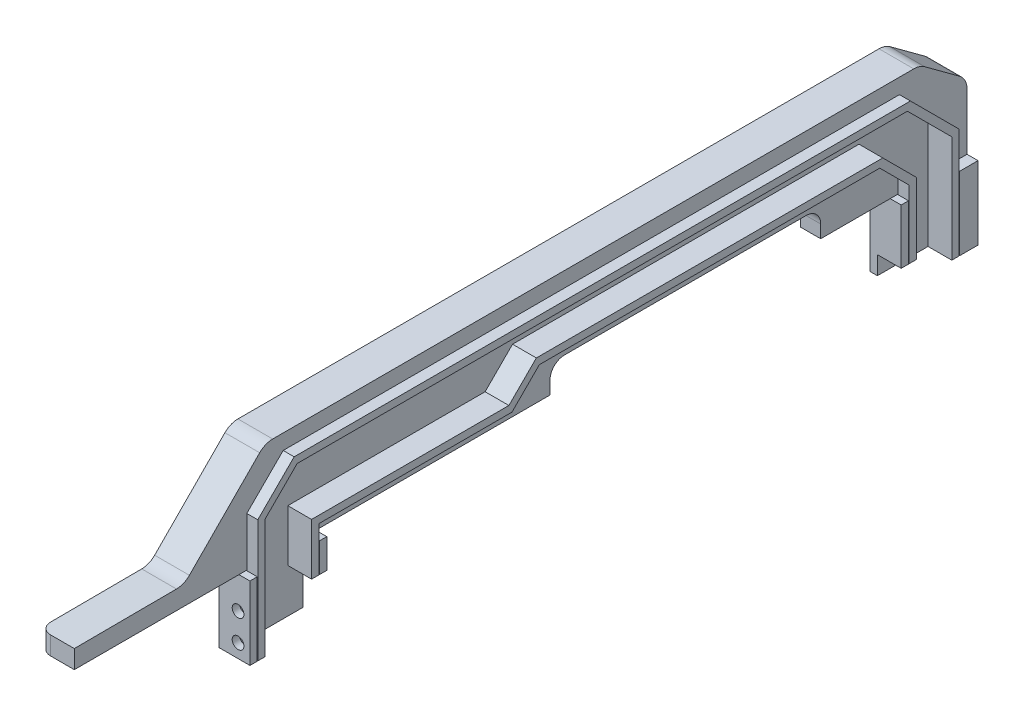
SolidWorks part; units mm, degrees
ref_plane "Front Plane" through (0, 0, 0) normal (0, 0, 1) x (1, 0, 0)
ref_plane "Top Plane" through (0, 0, 0) normal (0, 1, 0) x (1, 0, 0)
ref_plane "Right Plane" through (0, 0, 0) normal (1, 0, 0) x (0, 0, -1)
sketch "Sketch1" plane through (0, 0, 0) normal (1, 0, 0) x (0, 0, -1)
  line L0 (0, 0) -> (-130, 0)
  line L1 (0, 0) -> (74, 0) construction
  line L2 (0, 0) -> (0, 7.5)
  line L3 (0, 7.5) -> (74, 7.5)
  line L4 (74, 7.5) -> (74, 0)
  line L5 (74, 0) -> (114, 0)
  line L6 (-130, 0) -> (-130, 5)
  line L7 (-130, 5) -> (-100.0004, 5.1483)
  line L8 (-100.0004, 5.1483) -> (-77.8685, 27.5)
  line L9 (114, 0) -> (114, 18)
  line L10 (114, 18) -> (101.0882, 27.5)
  line L11 (101.0882, 27.5) -> (-77.8685, 27.5)
  dimension "D1" = 130
  dimension "D2" = 74
  dimension "D3" = 7.5
  dimension "D4" = 40
  dimension "D5" = 30
  dimension "D6" = 5
  dimension "D7" = 135
  dimension "D8" = 20
  dimension "D9" = 18
extrude "Boss-Extrude1" add sketch "Sketch1" along normal blind 25
sketch "Sketch4" plane through (25, 0, 0) normal (1, 0, 0) x (0, 0, -1)
  line L11 (-130, 0) -> (0, 0) construction
  line L12 (-130, 0) -> (0, 0) construction
  line L13 (-100.8762, 0) -> (0, 0)
  line L14 (0, 0) -> (111, 0)
  line L15 (74, 0) -> (114, 0) construction
  line L16 (111, 0) -> (111, 3)
  line L22 (-3, 3) -> (-3, 10.5)
  line L23 (-3, 10.5) -> (77, 10.5)
  line L24 (77, 10.5) -> (77, 3)
  line L25 (77, 3) -> (111, 3)
  line L26 (111, 3) -> (111, 16.4828)
  line L27 (111, 16.4828) -> (100.1035, 24.5)
  line L28 (100.1035, 24.5) -> (-76.6172, 24.5)
  line L29 (-76.6172, 24.5) -> (-97.9057, 3)
  line L30 (-97.9057, 3) -> (-3, 3)
  line L35 (111, 3) -> (111, 16.4828)
  line L36 (111, 16.4828) -> (100.1035, 24.5)
  line L37 (100.1035, 24.5) -> (-76.6172, 24.5)
  line L38 (-76.6172, 24.5) -> (-100.8762, 0)
  dimension "D1" = 3
extrude "Cut-Extrude1" cut sketch "Sketch4" against normal blind 4
ref_plane "Plane1" through (12.5, 0, 0) normal (1, 0, 0) x (0, 0, -1)
mirror "Mirror2" about plane through (12.5, 0, 0) normal (1, 0, 0) of "Cut-Extrude1"
fillet "Fillet1" radius 4 2 edges at (12.5, 7.5, -74) (12.5, 7.5, 0)
fillet "Fillet2" radius 10 8 edges at (23, 16.4828, -111) (23, 24.5, -100.1035) (2, 16.4828, -111) (2, 24.5, -100.1035) (2, 24.5, 76.6172) (23, 24.5, 76.6172) (2, 0, 100.8762) (23, 0, 100.8762)
fillet "Fillet3" radius 5 4 edges at (12.5, 18, -114) (12.5, 27.5, -101.0882) (12.5, 27.5, 77.8685) (12.5, 5.1483, 100.0004)
fillet "Fillet4" radius 3 2 edges at (0, 2.5, 130) (25, 2.5, 130)
sketch "Sketch5" plane through (12.5, 0, 0) normal (1, 0, 0) x (0, 0, -1)
  line L0 (-117.866, 5.06) -> (-103.7939, 19.2718)
  line L1 (-102.0714, 5.138) -> (-127, 5.0148) construction
  line L2 (-79.3359, 26.018) -> (-98.5432, 6.62) construction
  line L3 (-103.7939, 19.2718) -> (-72.6053, 19.2718)
  line L4 (-117.866, 5.06) -> (-95.866, 5.06)
  line L5 (-79.552, 21.536) -> (-97.9414, 2.964) construction
  line L6 (-72.6053, 19.2718) -> (-95.866, 5.06)
  dimension "D1" = 22
  dimension "D2" = 20
extrude "Boss-Extrude2" add sketch "Sketch5" along normal blind 3 and the other way blind 3
fillet "Fillet5" radius 3 1 edges at (12.5, 19.2718, 103.7939)
sketch "Sketch6" plane through (0, 0, 0) normal (0, -1, 0) x (1, 0, 0)
  line L1 (0, -111) -> (0, -114) construction
  line L2 (0, -111) -> (4, -111)
  line L3 (0, -111) -> (0, -114)
  line L4 (0, -114) -> (25, -114)
  line L5 (25, -111) -> (25, -114)
  line L6 (0, -111) -> (25, -114) construction
  line L7 (0, -114) -> (25, -111) construction
  line L8 (4, -111) -> (0, -111) construction
  line L9 (25, -114) -> (0, -114) construction
  line L10 (4, -74) -> (4, -111) construction
  line L11 (4, -111) -> (21, -111) construction
  line L12 (4, -111) -> (4, -93)
  line L13 (4, -93) -> (21, -93)
  line L14 (21, -111) -> (21, -93)
  line L15 (4, -111) -> (21, -93) construction
  line L16 (4, -93) -> (21, -111) construction
  line L17 (21, -74) -> (21, -111) construction
  line L18 (4, -111) -> (21, -111) construction
  line L19 (21, -111) -> (25, -111)
  line L21 (19, -95) -> (6, -95)
  line L22 (19, -95) -> (19, -109)
  line L23 (19, -109) -> (6, -109)
  line L24 (6, -95) -> (6, -109)
  line L25 (19, -95) -> (6, -109) construction
  line L26 (19, -109) -> (6, -95) construction
  point P6 (12.5, -112.5)
  point P16 (12.5, -102)
  point P21 (12.5, -102)
  dimension "D1" = 18
  dimension "D2" = 2
  dimension "D3" = 2
extrude "Boss-Extrude3" add sketch "Sketch6" along normal blind 20
sketch "Sketch7" plane through (0, -20, 0) normal (0, -1, 0) x (1, 0, 0)
  line L0 (19, -109) -> (19, -95) construction
  line L1 (19, -95) -> (6, -95)
  line L2 (19, -95) -> (19, -93)
  line L3 (19, -93) -> (6, -93)
  line L4 (6, -95) -> (6, -93)
  line L5 (19, -95) -> (6, -93) construction
  line L6 (19, -93) -> (6, -95) construction
  line L7 (19, -95) -> (6, -95) construction
  line L8 (21, -93) -> (4, -93) construction
  line L9 (6, -95) -> (6, -109) construction
  point P4 (12.5, -94)
sketch "Sketch8" plane through (0, 0, 0) normal (0, -1, 0) x (1, 0, 0)
  line L5 (21, 85) -> (21, 130) construction
  line L6 (21, 105.0473) -> (21, 0) construction
  line L8 (22, 130) -> (3, 130) construction
  line L9 (4, 105.0473) -> (4, 0) construction
  line L10 (21, 85) -> (4, 85)
  line L11 (21, 85) -> (21, 64)
  line L12 (21, 64) -> (19, 64)
  line L13 (4, 85) -> (4, 64)
  line L14 (21, 85) -> (4, 64) construction
  line L15 (21, 64) -> (4, 85) construction
  line L16 (19, 64) -> (6, 64) construction
  line L17 (6, 64) -> (19, 64) construction
  line L18 (6, 64) -> (6, 83)
  line L19 (6, 83) -> (19, 83)
  line L20 (19, 64) -> (19, 83)
  line L21 (6, 64) -> (19, 83) construction
  line L22 (6, 83) -> (19, 64) construction
  line L23 (6, 64) -> (4, 64)
  point P9 (12.5, 74.5)
  point P16 (12.5, 73.5)
  dimension "D1" = 45
  dimension "D2" = 21
  dimension "D3" = 2
  dimension "D4" = 2
  dimension "D5" = 2
extrude "Boss-Extrude4" add sketch "Sketch8" along normal blind 20
sketch "Sketch9" plane through (0, 0, 0) normal (0, -1, 0) x (1, 0, 0)
  line L0 (6, 64) -> (6, 83) construction
  line L1 (6, 64) -> (19, 64)
  line L2 (6, 64) -> (6, 66)
  line L3 (6, 66) -> (19, 66)
  line L4 (19, 64) -> (19, 66)
  line L5 (6, 64) -> (19, 66) construction
  line L6 (6, 66) -> (19, 64) construction
  line L7 (19, 83) -> (19, 64) construction
  point P4 (12.5, 65)
  dimension "D1" = 2
extrude "Boss-Extrude5" add sketch "Sketch9" along normal blind 8
extrude "Cut-Extrude2" cut sketch "Sketch7" against normal blind 5 contours L3 L4 L1 L2
sketch "Sketch11" plane through (0, 0, -114) normal (0, 0, -1) x (-1, 0, 0)
  line L0 (0, -20) -> (0, -12.5) construction
  line L1 (0, -20) -> (-25, -20) construction
  line L2 (0, -20) -> (0, 15.4713) construction
  line L3 (0, -16.25) -> (-25, -16.25) construction
  line L4 (-25, -20) -> (-25, 15.4713) construction
  line L5 (0, -16.25) -> (-9.25, -16.25) construction
  line L6 (-12.5, -20) -> (-12.5, -5) construction
  line L7 (0, -20) -> (0, -16.25)
  line L8 (-25, -20) -> (-25, -12.5) construction
  line L9 (-25, -12.5) -> (0, -12.5) construction
  circle A0 centre (-9.25, -16.25) radius 1.6
  circle A1 centre (-15.75, -16.25) radius 1.6
  circle A2 centre (-15.75, -8.75) radius 1.6
  circle A3 centre (-9.25, -8.75) radius 1.6
  circle A4 centre (-15.75, -16.25) radius 3 construction
  dimension "D2" = 3.2
  dimension "D5" = 6
  dimension "D1" = 9.25
  dimension "D3" = 3.75
  dimension "D4" = 7.5
extrude "Cut-Extrude3" cut sketch "Sketch11" against normal up to surface (19 mm away) contours A1 | A2 | A3 | A0 region at (9.25, -16.25, -114) region at (15.75, -16.25, -114) region at (15.75, -8.75, -114) region at (9.25, -8.75, -114) up to face at (12.5, -7.5, -95)
sketch "Sketch12" plane through (0, 0, 85) normal (0, 0, 1) x (1, 0, 0)
  line L0 (15.75, -8.75) -> (21, -8.75) construction
  line L1 (15.75, -8.75) -> (15.75, -5) construction
  line L3 (12.5, -20) -> (12.5, -5) construction
  line L6 (0, -12.5) -> (25, -12.5) construction
  line L7 (4, -20) -> (21, -20) construction
  line L8 (4, -20) -> (4, 0) construction
  line L9 (21, -20) -> (21, 0) construction
  circle A0 centre (15.75, -16.25) radius 1.6
  circle A1 centre (9.25, -16.25) radius 1.6
  circle A2 centre (9.25, -8.75) radius 1.6
  circle A3 centre (15.75, -8.75) radius 1.6
  circle A4 centre (9.25, -16.25) radius 3 construction
  dimension "D1" = 3.2
  dimension "D2" = 5.25
  dimension "D3" = 3.75
extrude "Cut-Extrude4" cut sketch "Sketch12" against normal up to surface (2 mm away) up to face at (12.5, -10, 83)
sketch "MAKE THIS A SQUARE OR SMTH" plane through (4, 0, 0) normal (-1, 0, 0) x (0, 0, 1)
  line L0 (-37, 7.5) -> (-37, 24.5) construction
  line L1 (-70, 7.5) -> (-4, 7.5) construction
  line L2 (-96.8211, 24.5) -> (72.4461, 24.5) construction
  line L3 (-37, 16) -> (-111, 16) construction
  line L4 (-37, 16) -> (84, 16) construction
  line L6 (-111, 16) -> (-13.5, 16) construction
  line L7 (-13.5, 16) -> (-13.5, 7.5) construction
  line L8 (-111, 16) -> (-91, 16) construction
  circle A1 centre (-91, 16) radius 6.5
  circle A2 centre (-39.3333, 16) radius 6.5
  circle A3 centre (64, 16) radius 6.5
  circle A4 centre (12.3333, 16) radius 6.5
  dimension "D5" = 13
  dimension "D1" = 74
  dimension "D2" = 121
  dimension "D3" = 97.5
  dimension "D4" = 20
  dimension "D6" = 51.6667
sketch "Sketch14" plane through (12.5, 0, 0) normal (1, 0, 0) x (0, 0, -1)
  line L0 (-83, 0) -> (-83, 13.4752)
  line L1 (-66, 0) -> (-66, 4)
  line L2 (-66, 4) -> (-13.3251, 4)
  line L3 (-13.3251, 4) -> (-5.8251, 11.5)
  line L4 (-5.8251, 11.5) -> (87.0794, 11.5)
  line L5 (95, 0) -> (95, 3.5794)
  line L6 (95, 3.5794) -> (87.0794, 11.5)
  line L7 (109, 0) -> (109, 10.0924)
  line L8 (109, -20) -> (109, 0) construction
  line L9 (95, 0) -> (109, 0) construction
  line L10 (109, 10.0924) -> (95.5924, 23.5)
  line L15 (-72.9752, 23.5) -> (-83, 13.4752)
  line L16 (-83, 0) -> (-66, 0)
  line L17 (95, 0) -> (109, 0)
  line L18 (95.5924, 23.5) -> (-72.9752, 23.5)
  line L19 (-64, 0) -> (0, 0) construction
  line L20 (99.447, 27.5) -> (-75.783, 27.5) construction
  line L21 (70, 7.5) -> (4, 7.5) construction
  dimension "D1" = 135
  dimension "D2" = 135
  dimension "D3" = 135
  dimension "D4" = 135
  dimension "D5" = 4
  dimension "D6" = 4
  dimension "D7" = 4
extrude "Cut-Extrude5" cut sketch "Sketch14" against normal blind 6.5 and the other way blind 6.5
sketch "Sketch17" plane through (0, 0, 130) normal (0, 0, 1) x (1, 0, 0)
  line L0 (12.5, -20) -> (25, -20)
  line L1 (21, -20) -> (4, -20) construction
  line L2 (25, -20) -> (25, 27.5)
  line L3 (25, 27.5) -> (9.5, 27.5)
  line L4 (0, 27.5) -> (25, 27.5) construction
  line L5 (9.5, 5.138) -> (9.5, 27.5)
  line L6 (12.5, -20) -> (12.5, 0)
  line L7 (22, 0) -> (3, 0) construction
  line L8 (12.5, 0) -> (9.5, 0)
  line L9 (21, 0) -> (4, 0) construction
  line L10 (9.5, 0) -> (9.5, 5.138)
extrude "Cut-Extrude7" cut sketch "Sketch17" against normal through all
sketch "Sketch18" plane through (6, 0, 0) normal (1, 0, 0) x (0, 0, -1)
  line L0 (-83, -20) -> (-82.85, -20)
  line L1 (-64, -20) -> (-83, -20) construction
  line L2 (-82.85, -20) -> (-80.85, -20)
  line L3 (-66, -8) -> (-66.15, -8)
  line L4 (-66.15, -8) -> (-68.15, -8)
  line L5 (-66.15, -8) -> (-66.15, 4.15)
  line L6 (-66.15, 4.15) -> (-13.3872, 4.15)
  line L7 (-13.3872, 4.15) -> (-5.8872, 11.65)
  line L8 (-5.8872, 11.65) -> (87.1415, 11.65)
  line L9 (87.1415, 11.65) -> (95.15, 3.6415)
  line L10 (95.15, 3.6415) -> (95.15, -15)
  line L11 (95, -15) -> (95, 3.5794) construction
  line L12 (95, -15) -> (95.15, -15)
  line L13 (95, 3.5794) -> (87.0794, 11.5) construction
  line L14 (-47.2142, 4) -> (-47.2142, 4.15) construction
  line L15 (-13.3251, 4) -> (-66, 4) construction
  line L16 (-10.7524, 6.7848) -> (-10.6464, 6.6787) construction
  line L17 (-68.15, -10) -> (-68.15, 6.15) construction
  line L18 (-5.8251, 11.5) -> (-13.3251, 4) construction
  line L19 (91.2889, 7.2905) -> (91.3949, 7.3966) construction
  line L20 (61.1672, 11.5) -> (61.1672, 11.65) construction
  line L21 (-5.8251, 11.5) -> (87.0794, 11.5) construction
  line L22 (95.15, -15) -> (97.15, -15)
  line L23 (-68.15, -8) -> (-68.15, 6.15)
  line L24 (-68.15, 6.15) -> (-14.2157, 6.15)
  line L25 (-14.2157, 6.15) -> (-6.7157, 13.65)
  line L26 (-6.7157, 13.65) -> (87.97, 13.65)
  line L27 (87.97, 13.65) -> (97.15, 4.47)
  line L28 (97.15, 4.47) -> (97.15, -15)
  line L29 (-82.85, -20) -> (-82.85, 13.413)
  line L30 (-49.2142, 4) -> (-49.2142, 4.15) construction
  line L31 (-9.3382, 8.199) -> (-9.2321, 8.093) construction
  line L32 (89.8746, 8.7048) -> (89.9807, 8.8108) construction
  line L33 (59.1672, 11.5) -> (59.1672, 11.65) construction
  line L34 (-66, -10) -> (-68.15, -10) construction
  line L35 (97.15, 4.47) -> (97.15, -17) construction
  line L36 (95, -17) -> (97.15, -17) construction
  line L37 (-82.85, 13.413) -> (-72.913, 23.35)
  line L38 (-72.9752, 23.5) -> (-83, 13.4752) construction
  line L39 (-72.913, 23.35) -> (95.5303, 23.35)
  line L40 (-78.8315, 17.4315) -> (-78.9376, 17.5376) construction
  line L41 (-83, -20) -> (-83, 13.4752)
  line L42 (-68.3764, 23.35) -> (-68.3764, 23.5) construction
  line L43 (-72.9752, 23.5) -> (95.5924, 23.5) construction
  line L44 (95.5303, 23.35) -> (108.85, 10.0303)
  line L45 (108.85, 10.0303) -> (108.85, -20)
  line L46 (93, -20) -> (109, -20) construction
  line L47 (109, 10.0924) -> (95.5924, 23.5) construction
  line L48 (101.5774, 17.3029) -> (101.6835, 17.4089) construction
  line L49 (108.85, -12.75) -> (109, -12.75) construction
  line L50 (109, 0) -> (109, -20) construction
  line L51 (-80.85, -20) -> (-80.85, 12.5846)
  line L52 (-80.85, 12.5846) -> (-72.0846, 21.35)
  line L53 (-72.0846, 21.35) -> (94.7019, 21.35)
  line L54 (94.7019, 21.35) -> (106.85, 9.2019)
  line L55 (106.85, 9.2019) -> (106.85, -20)
  line L56 (-82.85, -20) -> (-80.85, -20)
  line L57 (106.85, -20) -> (108.85, -20)
  line L58 (-83, 13.4752) -> (-72.9752, 23.5) construction
  line L59 (-83, 13.4752) -> (-72.9752, 23.5)
  line L60 (-72.9752, 23.5) -> (95.5924, 23.5)
  line L61 (95.5924, 23.5) -> (109, 10.0924)
  line L62 (109, 10.0924) -> (109, -20)
  line L63 (109, -20) -> (108.85, -20)
  line L64 (-66, -8) -> (-66, 4)
  line L65 (-66, 4) -> (-13.3251, 4)
  line L66 (-13.3251, 4) -> (-5.8251, 11.5)
  line L67 (-5.8251, 11.5) -> (87.0794, 11.5)
  line L68 (87.0794, 11.5) -> (95, 3.5794)
  line L69 (95, 3.5794) -> (95, -15)
  line L70 (-66.1464, -8) -> (-66, -8)
  point P105 (0, 0)
  dimension "D1" = 0.15
  dimension "D3" = 2
extrude "Boss-Extrude6" add sketch "Sketch18" along normal up to surface (6.5 mm away) contours L54 L55 L19 L45 L44 L39 L37 L29 L5 L51 L52 L53 L48 L6 | L5 L6 L7 L8 L9 L10 L22 L28 L27 L26 L25 L24 L23 L4 region at (6, -3.2935, 80.8846) up to face at (12.5, -10, 84)
sketch "Sketch24" plane through (6, 0, 0) normal (1, 0, 0) x (0, 0, -1)
  line L0 (-83, -20) -> (-82.85, -20)
  line L1 (-82.85, -20) -> (-82.85, 13.413)
  line L2 (-82.85, 13.413) -> (-72.913, 23.35)
  line L3 (-72.913, 23.35) -> (95.5303, 23.35)
  line L4 (95.5303, 23.35) -> (108.85, 10.0303)
  line L5 (108.85, 10.0303) -> (108.85, -20)
  line L6 (108.85, -20) -> (109, -20)
  line L7 (109, -20) -> (109, 10.0924)
  line L8 (109, 10.0924) -> (95.5924, 23.5)
  line L9 (95.5924, 23.5) -> (-72.9752, 23.5)
  line L10 (-72.9752, 23.5) -> (-83, 13.4752)
  line L11 (-83, 13.4752) -> (-83, -20)
  line L12 (-66.15, -8) -> (-66, -8)
  line L13 (-66, -8) -> (-66, 4)
  line L14 (-66, 4) -> (-13.3251, 4)
  line L15 (-13.3251, 4) -> (-5.8251, 11.5)
  line L16 (-5.8251, 11.5) -> (87.0794, 11.5)
  line L17 (87.0794, 11.5) -> (95, 3.5794)
  line L18 (95, 3.5794) -> (95, -15)
  line L19 (95, -15) -> (95.15, -15)
  line L20 (95.15, -15) -> (95.15, 3.6415)
  line L21 (95.15, 3.6415) -> (87.1415, 11.65)
  line L22 (87.1415, 11.65) -> (-5.8872, 11.65)
  line L23 (-5.8872, 11.65) -> (-13.3872, 4.15)
  line L24 (-13.3872, 4.15) -> (-66.15, 4.15)
  line L25 (-66.15, 4.15) -> (-66.15, -8)
extrude "Boss-Extrude8" add sketch "Sketch24" along normal up to surface (3.5 mm away) contours L1 L2 L3 L4 L5 L6 L7 L8 L9 L10 L11 L0 | L13 L14 L15 L16 L17 L18 L19 L20 L21 L22 L23 L24 L25 L12 up to face at (9.5, 12.7959, 4.6522)
